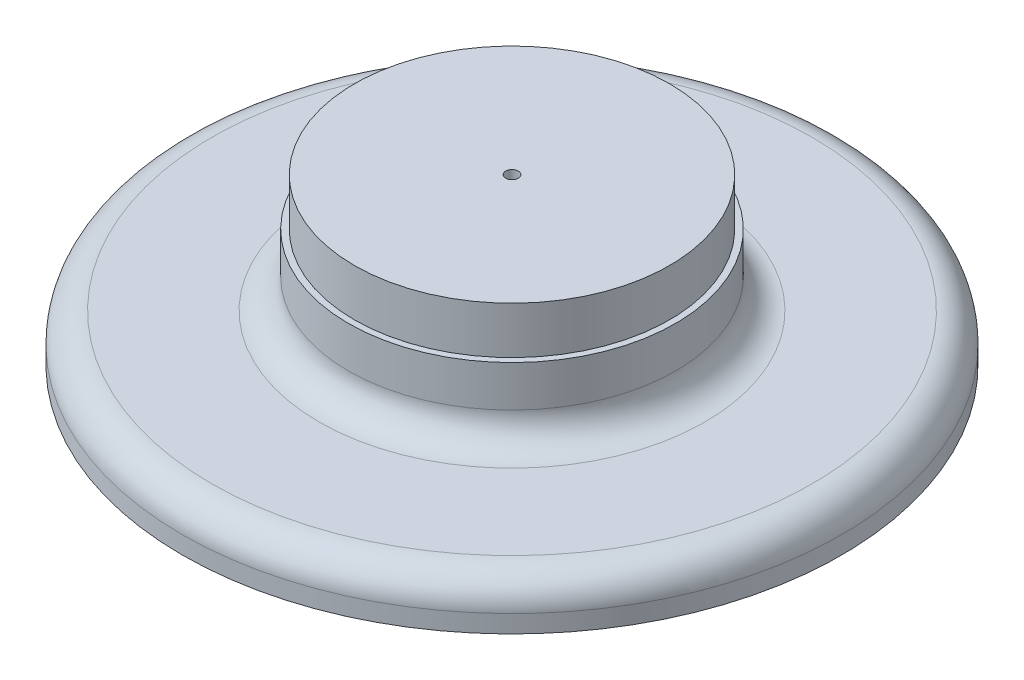
SolidWorks part; units mm, degrees
ref_plane "Front Plane" through (0, 0, 0) normal (0, 0, 1) x (1, 0, 0)
ref_plane "Top Plane" through (0, 0, 0) normal (0, 1, 0) x (1, 0, 0)
ref_plane "Right Plane" through (0, 0, 0) normal (1, 0, 0) x (0, 0, -1)
sketch "Sketch1" plane through (0, 0, 0) normal (0, 1, 0) x (1, 0, 0)
  circle A0 centre (0, 0) radius 84.9884
  circle A1 centre (0, 0) radius 88.265
  circle A2 centre (0, 0) radius 177.8
extrude "Boss-Extrude1" add sketch "Sketch1" along normal blind 88.9 contours A0 region at (0, 0, 0)
extrude "Boss-Extrude2" add sketch "Sketch1<3>" along normal blind 63.5 contours A1 A0 region at (-85.7685, 0, 0)
sketch "Sketch1<3>" plane through (0, 0, 0) normal (0, 1, 0) x (1, 0, 0) same geometry as "Sketch1"
extrude "Boss-Extrude3" add sketch "Sketch1<4>" along normal blind 25.4 contours A2 A1 region at (-172.7711, 0, 0)
sketch "Sketch1<4>" plane through (0, 0, 0) normal (0, 1, 0) x (1, 0, 0) same geometry as "Sketch1"
hole_wizard "CSK for 1/4 Flat Head Machine Screw (100)1" positions "Sketch2" profile "Sketch3" countersink size "1/4" standard "ANSI Inch" end condition through all
sketch "Sketch2" plane through (0, 0, 0) normal (0, -1, 0) x (-1, 0, 0)
  point P0 (0, 0)
sketch "Sketch3" plane through (0, 0, 0) normal (1, 0, 0) x (0, 0, -1)
  line L0 (0, 0) -> (0, 88.9)
  line L1 (0, 88.9) -> (3.3782, 88.9)
  line L2 (3.3782, 88.9) -> (3.3782, 2.5682)
  line L3 (3.3782, 2.5682) -> (6.4389, 0)
  line L5 (6.4389, 0) -> (0, 0)
  line L6 (-3.3782, 2.5682) -> (-6.4389, 0) construction
  line L11 (0, -6.35) -> (0, 107.95) construction
  dimension "Thru Hole Dia." = 6.7564
  dimension "Thru Hole Depth" = 88.9
  dimension "Near C'Sink Dia." = 12.8778
  dimension "Near C'Sink Angle" = 100
fillet "Fillet1" radius 15.875 1 edges at (0, 25.4, 88.265)
fillet "Fillet2" radius 15.875 1 edges at (0, 25.4, 177.8)
